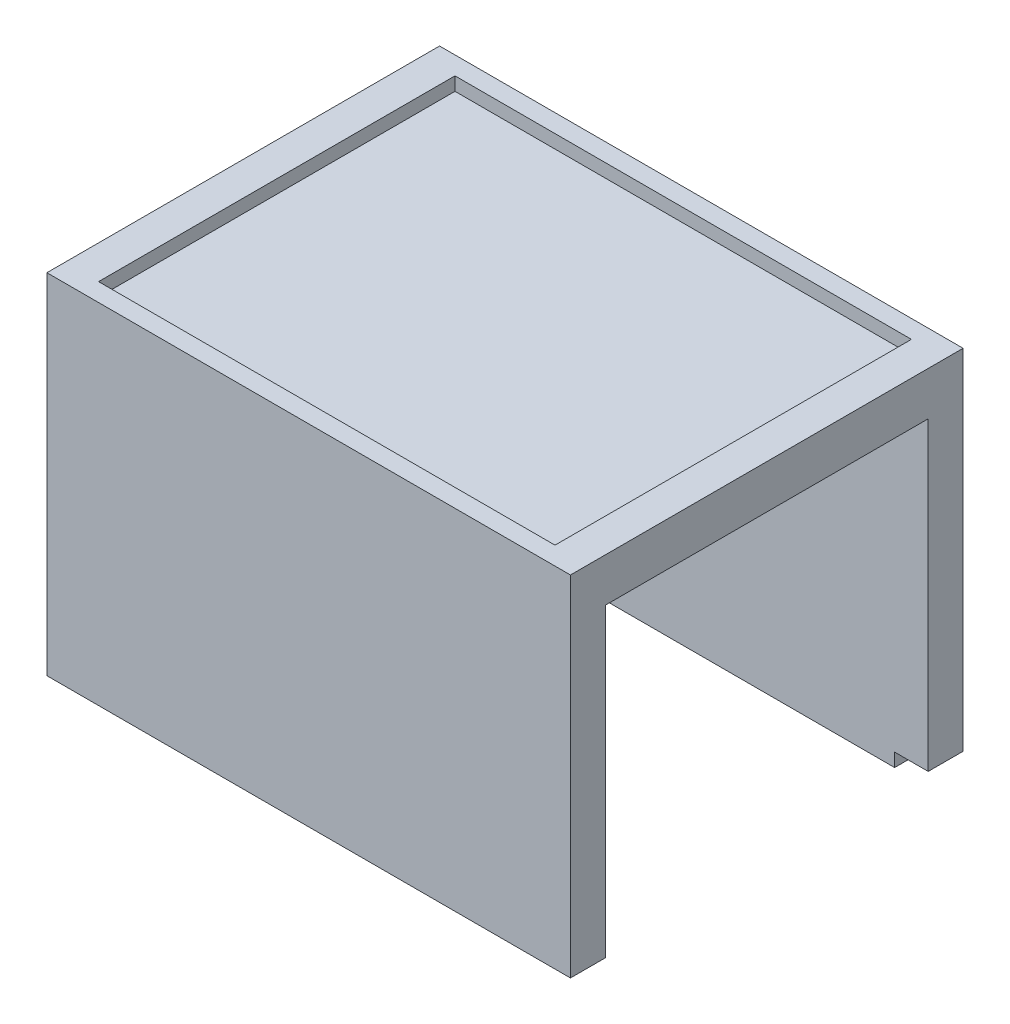
SolidWorks part; units mm, degrees
ref_plane "Front Plane" through (0, 0, 0) normal (0, 0, 1) x (1, 0, 0)
ref_plane "Top Plane" through (0, 0, 0) normal (0, 1, 0) x (1, 0, 0)
ref_plane "Right Plane" through (0, 0, 0) normal (1, 0, 0) x (0, 0, -1)
sketch "Sketch1" plane through (0, 0, 0) normal (0, 1, 0) x (1, 0, 0)
  line L1 (-19.5, 14.625) -> (19.5, 14.625)
  line L2 (-19.5, 14.625) -> (-19.5, -14.625)
  line L3 (-19.5, -14.625) -> (19.5, -14.625)
  line L4 (19.5, 14.625) -> (19.5, -14.625)
  line L5 (-19.5, 14.625) -> (19.5, -14.625) construction
  line L6 (-19.5, -14.625) -> (19.5, 14.625) construction
  point P0 (0, 0)
  dimension "D1" = 39
  dimension "D2" = 29.25
extrude "Boss-Extrude1" add sketch "Sketch1" along normal blind 3.25
sketch "Sketch2" plane through (0, 3.25, 0) normal (0, 1, 0) x (1, 0, 0)
  line L1 (-17, 12) -> (17, 12)
  line L2 (-17, 12) -> (-17, -12)
  line L3 (-17, -12) -> (17, -12)
  line L4 (17, 12) -> (17, -12)
  line L5 (-17, 12) -> (17, -12) construction
  line L6 (-17, -12) -> (17, 12) construction
  point P0 (0, 0)
  dimension "D1" = 34
  dimension "D2" = 24
extrude "Cut-Extrude1" cut sketch "Sketch2" against normal blind 1
sketch "Sketch3" plane through (0, 3.25, 0) normal (0, 1, 0) x (1, 0, 0)
  line L0 (-17, -12) -> (17, -12) construction
  line L1 (-17, -12) -> (17, -12)
  line L2 (-17, -12) -> (-17, -13.275)
  line L3 (-17, -13.275) -> (17, -13.275)
  line L4 (17, -12) -> (17, -13.275)
  line L5 (-17, -12) -> (17, -13.275) construction
  line L6 (-17, -13.275) -> (17, -12) construction
  line L7 (-17, 12) -> (-17, -12) construction
  point P0 (0, -12.6375)
  dimension "D1" = 1.275
extrude "Cut-Extrude2" cut sketch "Sketch3" against normal blind 1
mirror "Mirror1" about plane through (0, 0, 0) normal (0, 0, 1) of "Cut-Extrude2"
sketch "Sketch4" plane through (0, 0, 14.625) normal (0, 0, 1) x (1, 0, 0)
  line L0 (-19.5, 0) -> (19.5, 0) construction
  line L1 (-19.5, 0) -> (19.5, 0)
  line L2 (-19.5, 0) -> (-19.5, -22.75)
  line L3 (-19.5, -22.75) -> (19.5, -22.75)
  line L4 (19.5, 0) -> (19.5, -22.75)
  line L5 (-19.5, 0) -> (19.5, -22.75) construction
  line L6 (-19.5, -22.75) -> (19.5, 0) construction
  line L7 (-19.5, 3.25) -> (-19.5, 0) construction
  point P0 (0, -11.375)
  dimension "D1" = 22.75
extrude "Boss-Extrude2" add sketch "Sketch4" against normal blind 2.6
sketch "Sketch6" plane through (0, -22.75, 0) normal (0, -1, 0) x (1, 0, 0)
  line L0 (-19.5, 12.025) -> (19.5, 12.025) construction
  line L1 (-17, 13.275) -> (17, 13.275)
  line L2 (-17, 13.275) -> (-17, 12.025)
  line L3 (-17, 12.025) -> (17, 12.025)
  line L4 (17, 13.275) -> (17, 12.025)
  line L5 (-17, 13.275) -> (17, 12.025) construction
  line L6 (-17, 12.025) -> (17, 13.275) construction
  point P0 (0, 12.65)
  dimension "D1" = 1.25
  dimension "D2" = 34
extrude "Boss-Extrude3" add sketch "Sketch6" along normal blind 1
mirror "Mirror2" about plane through (0, 0, 0) normal (0, 0, 1) of "Boss-Extrude3", "Boss-Extrude2"
